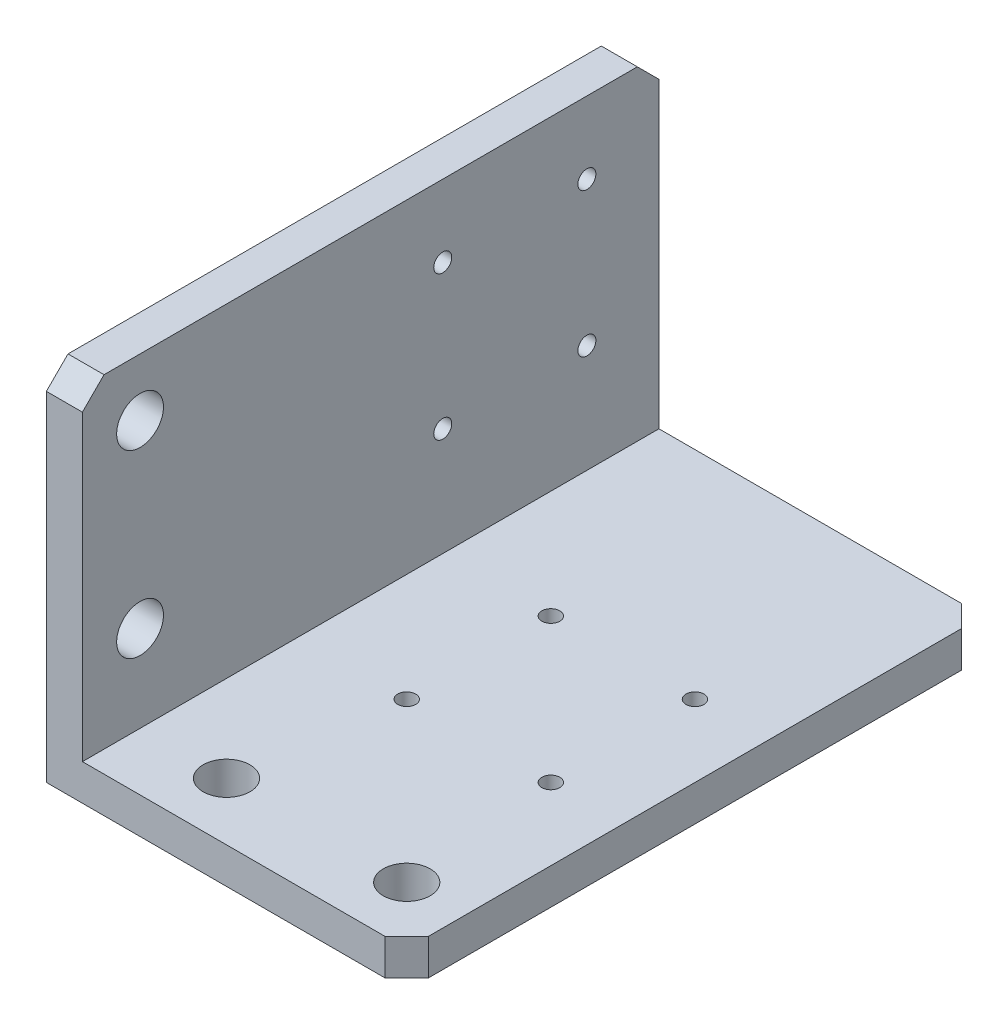
SolidWorks part; units mm, degrees
material "Lega 1060"
ref_plane "Piano frontale" through (0, 0, 0) normal (0, 0, 1) x (1, 0, 0)
ref_plane "Piano superiore" through (0, 0, 0) normal (0, 1, 0) x (1, 0, 0)
ref_plane "Piano destro" through (0, 0, 0) normal (1, 0, 0) x (0, 0, -1)
sketch "Schizzo1" plane through (0, 0, 0) normal (0, 0, 1) x (1, 0, 0)
  line L0 (0, 0) -> (0, 50)
  line L1 (0, 50) -> (5, 50)
  line L2 (5, 50) -> (5, 5)
  line L3 (5, 5) -> (50, 5)
  line L4 (50, 5) -> (50, 0)
  line L5 (50, 0) -> (0, 0)
  dimension "D1" = 5
  dimension "D2" = 5
  dimension "D3" = 50
  dimension "D4" = 50
extrude "Estrusione-Estrusione1" add sketch "Schizzo1" along normal blind 80
sketch "Schizzo2" plane through (0, 0, 0) normal (0, -1, 0) x (1, 0, 0)
  line L0 (5.4524, 72) -> (42.7933, 72) construction
  line L1 (0, 80) -> (50, 80) construction
  line L5 (50, 80) -> (50, 0) construction
  point P4 (17, 72)
  point P5 (42, 72)
  dimension "D1" = 8
  dimension "D2" = 25
  dimension "D3" = 8
sketch "Schizzo3" plane through (0, 0, 0) normal (-1, 0, 0) x (0, 0, 1)
  line L0 (72, 44.621) -> (72, 5.772) construction
  line L1 (80, 50) -> (80, 0) construction
  line L2 (80, 50) -> (0, 50) construction
  point P4 (72, 42)
  point P5 (72, 17)
  dimension "D1" = 8
  dimension "D2" = 8
  dimension "D3" = 25
hole_wizard "Foro Ø6.5 (6.5)-1" positions "Schizzo5" profile "Schizzo4" hole size "Ø6.5" standard "ISO" end condition through all
sketch "Schizzo5" plane through (0, 0, 0) normal (0, -1, 0) x (-1, 0, 0)
  point P0 (-17, -72)
  point P3 (-42, -72)
sketch "Schizzo4" plane through (17, 0, 72) normal (1, 0, 0) x (0, 0, -1)
  line L0 (0, 0) -> (0, 50)
  line L1 (0, 50) -> (3.25, 50)
  line L2 (3.25, 50) -> (3.25, 0)
  line L5 (3.25, 0) -> (0, 0)
  line L11 (0, -6.35) -> (0, 107.95) construction
  dimension "Thru Hole Dia." = 6.5
  dimension "Thru Hole Depth" = 50
hole_wizard "Foro Ø6.5 (6.5)-2" positions "Schizzo7" profile "Schizzo6" hole size "Ø6.5" standard "ISO"
sketch "Schizzo7" plane through (0, 0, 0) normal (-1, 0, 0) x (0, 0, 1)
  point P1 (72, 42)
  point P4 (72, 17)
sketch "Schizzo6" plane through (0, 42, 72) normal (0, 1, 0) x (0, 0, 1)
  line L0 (0, 0) -> (0, 6.9528)
  line L1 (0, 6.9528) -> (3.25, 5)
  line L2 (3.25, 5) -> (3.25, 0)
  line L5 (3.25, 0) -> (0, 0)
  line L10 (0, 6.9528) -> (-3.25, 5) construction
  line L11 (0, -6.35) -> (0, 107.95) construction
  dimension "Hole Dia." = 6.5
  dimension "Hole Depth" = 5
  dimension "Drill Angle" = 118
ref_plane "Piano1" through (0, 0, 40) normal (0, 0, 1) x (1, 0, 0)
sketch "Schizzo8" plane through (0, 0, 0) normal (-1, 0, 0) x (0, 0, 1)
  line L2 (80, 50) -> (80, 0) construction
  line L3 (80, 50) -> (0, 50) construction
  circle A0 centre (20, 30) radius 7
  dimension "D3" = 14
  dimension "D1" = 60
  dimension "D2" = 20
sketch "Schizzo9" plane through (0, 0, 0) normal (0, -1, 0) x (1, 0, 0)
  line L0 (50, 80) -> (50, 0) construction
  line L1 (0, 80) -> (50, 80) construction
  circle A0 centre (30, 40) radius 7
  dimension "D1" = 14
  dimension "D2" = 20
  dimension "D3" = 40
sketch "Schizzo10" plane through (0, 0, 0) normal (-1, 0, 0) x (0, 0, 1)
  line L1 (20, 42.2663) -> (20, 14.8621) construction
  line L2 (19.1906, 30.8094) -> (20, 30) construction
  circle A0 centre (10, 40) radius 1.75
  circle A1 centre (30, 40) radius 1.75
  circle A3 centre (30, 20) radius 1.75
  circle A4 centre (10, 20) radius 1.75
  circle A5 centre (20, 30) radius 7 construction
  point P20 (20, 30)
  dimension "D1" = 3.5
  dimension "D2" = 20
  dimension "D3" = 45
  dimension "D4" = 4
sketch "Schizzo11" plane through (0, 0, 0) normal (0, -1, 0) x (1, 0, 0)
  line L0 (30, 40) -> (14.4837, 40) construction
  line L1 (30, 40) -> (34.5929, 44.5929) construction
  circle A0 centre (20, 30) radius 1.75
  circle A3 centre (20, 50) radius 1.75
  circle A4 centre (40, 50) radius 1.75
  circle A5 centre (40, 30) radius 1.75
  circle A6 centre (30, 40) radius 7 construction
  point P2 (30, 40)
  point P17 (30, 40)
  dimension "D2" = 3.5
  dimension "D1" = 20
  dimension "D3" = 45
  dimension "D4" = 4
chamfer "Smusso1" distance 3 angle 45 4 edges at (2.5, 50, 0) (50, 2.5, 0) (2.5, 50, 80) (50, 2.5, 80)
hole_wizard "M3 Tapped Hole1" positions "3DSketch2" profile "Sketch2" tap size "M3" standard "ISO" end condition through all
sketch3d "3DSketch2"
  point P0 (0, 40, 10)
  point P3 (0, 40, 30)
  point P6 (0, 20, 30)
  point P9 (0, 20, 10)
sketch "Sketch2" plane through (0, 40, 10) normal (0, 1, 0) x (0, 0, 1)
  line L0 (0, 0) -> (0, 50)
  line L1 (0, 50) -> (1.25, 50)
  line L2 (1.25, 50) -> (1.25, 0)
  line L5 (1.25, 0) -> (0, 0)
  line L11 (0, -6.35) -> (0, 107.95) construction
  dimension "Thru Tap Drill Dia." = 2.5
  dimension "Thru Tap Drill Depth" = 50
cosmetic thread "Cosmetic Thread1" parameters "D2"=3
cosmetic thread "Cosmetic Thread2" parameters "D2"=3
cosmetic thread "Cosmetic Thread3" parameters "D2"=3
cosmetic thread "Cosmetic Thread4" parameters "D2"=3
hole_wizard "M3 Tapped Hole2" positions "3DSketch3" profile "Sketch3" tap size "M3" standard "ISO" end condition through all
sketch3d "3DSketch3"
  point P0 (20, 0, 50)
  point P3 (40, 0, 50)
  point P6 (40, 0, 30)
  point P9 (20, 0, 30)
sketch "Sketch3" plane through (20, 0, 50) normal (1, 0, 0) x (0, 0, -1)
  line L0 (0, 0) -> (0, 50)
  line L1 (0, 50) -> (1.25, 50)
  line L2 (1.25, 50) -> (1.25, 0)
  line L5 (1.25, 0) -> (0, 0)
  line L11 (0, -6.35) -> (0, 107.95) construction
  dimension "Thru Tap Drill Dia." = 2.5
  dimension "Thru Tap Drill Depth" = 50
cosmetic thread "Cosmetic Thread5" parameters "D2"=3
cosmetic thread "Cosmetic Thread6" parameters "D2"=3
cosmetic thread "Cosmetic Thread7" parameters "D2"=3
cosmetic thread "Cosmetic Thread8" parameters "D2"=3
